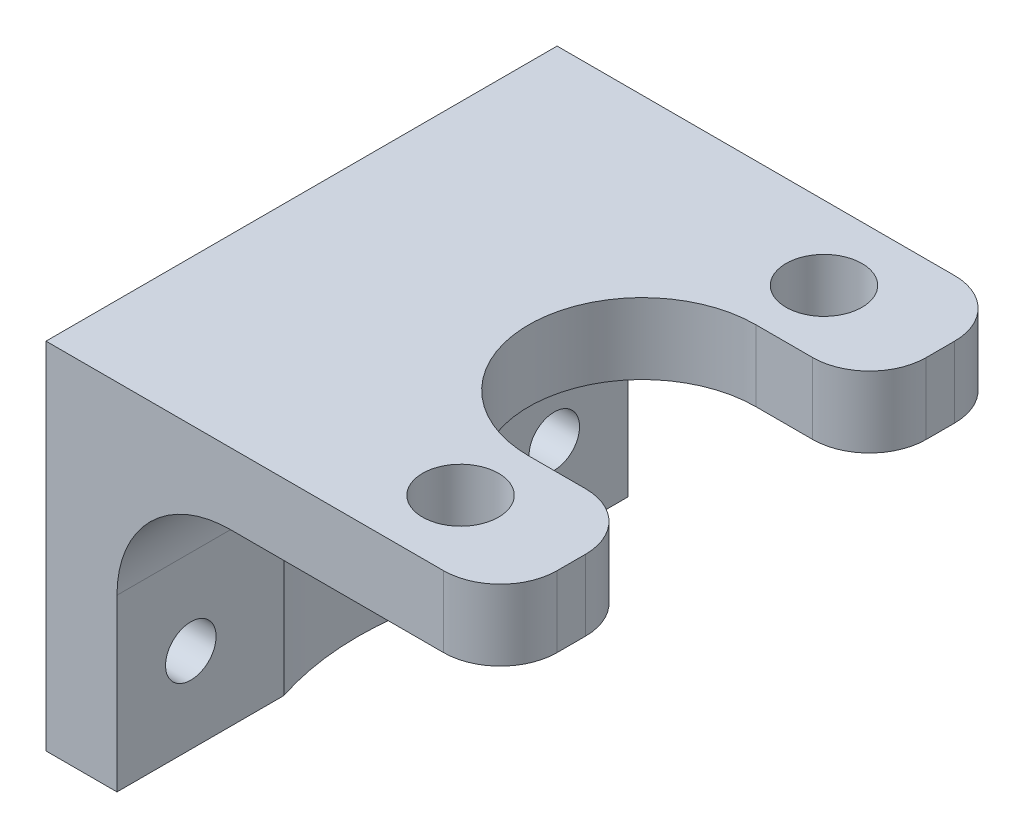
SolidWorks part; units mm, degrees
ref_plane "Front Plane" through (0, 0, 0) normal (0, 0, 1) x (1, 0, 0)
ref_plane "Top Plane" through (0, 0, 0) normal (0, 1, 0) x (1, 0, 0)
ref_plane "Right Plane" through (0, 0, 0) normal (1, 0, 0) x (0, 0, -1)
sketch "Sketch1" plane through (0, 0, 0) normal (0, 1, 0) x (1, 0, 0)
  line L1 (-10.16, -11.43) -> (10.16, -11.43)
  line L2 (-10.16, -11.43) -> (-10.16, 11.43)
  line L3 (-10.16, 11.43) -> (10.16, 11.43)
  line L4 (10.16, -11.43) -> (10.16, 11.43)
  line L5 (-10.16, -11.43) -> (10.16, 11.43) construction
  line L6 (-10.16, 11.43) -> (10.16, -11.43) construction
  point P0 (0, 0)
  dimension "D1" = 20.32
  dimension "D2" = 22.86
extrude "Boss-Extrude1" add sketch "Sketch1" along normal blind 3.175
fillet "Fillet1" radius 2.54 1 edges at (10.16, 1.5875, -11.43) type face fillet first side face at (10.16, 1.5875, 0) second side face at (0, 1.5875, -11.43)
fillet "Fillet2" radius 2.54 1 edges at (10.16, 1.5875, 11.43) type face fillet first side face at (10.16, 1.5875, 1.27) second side face at (0, 1.5875, 11.43)
sketch "Sketch2" plane through (0, 0, 0) normal (0, -1, 0) x (1, 0, 0)
  line L0 (-10.16, -11.43) -> (-10.16, 11.43) construction
  line L1 (7.62, -11.43) -> (-10.16, -11.43) construction
  line L2 (5.08, -5.08) -> (10.16, -5.08)
  line L3 (10.16, 8.89) -> (10.16, -8.89) construction
  line L4 (5.08, 5.08) -> (10.16, 5.08)
  line L5 (10.16, 5.08) -> (10.16, -5.08)
  arc A0 (5.08, 5.08) -> (5.08, -5.08) centre (5.08, 0) ccw
  dimension "D1" = 10.16
  dimension "D2" = 15.24
  dimension "D3" = 11.43
  dimension "D4" = 5.08
extrude "Cut-Extrude2" cut sketch "Sketch2" against normal through all
fillet "Fillet3" radius 2.54 1 edges at (10.16, 1.5875, 5.08) type face fillet first side face at (10.16, 1.5875, 6.985) second side face at (7.62, 1.5875, 5.08)
fillet "Fillet4" radius 2.54 1 edges at (10.16, 1.5875, -5.08) type face fillet first side face at (10.16, 1.5875, -6.985) second side face at (7.62, 1.5875, -5.08)
sketch "Sketch4" plane through (0, 0, 0) normal (0, -1, 0) x (1, 0, 0)
  line L0 (7.62, -11.43) -> (-10.16, -11.43) construction
  line L1 (-10.16, 11.43) -> (-6.985, 11.43)
  line L2 (-10.16, 11.43) -> (-10.16, -11.43)
  line L3 (-10.16, -11.43) -> (-6.985, -11.43)
  line L4 (-6.985, 11.43) -> (-6.985, -11.43)
  dimension "D1" = 3.175
extrude "Boss-Extrude2" add sketch "Sketch4" along normal blind 12.7
fillet "Fillet6" radius 5.08 1 edges type face fillet first side face at (5.3612, 0, -0.9525) second side face at (-6.985, -9.525, -2.8575)
sketch "Sketch3" plane through (0, 0, 0) normal (0, -1, 0) x (1, 0, 0)
  line L0 (7.62, -11.43) -> (-1.905, -11.43) construction
  line L1 (-1.905, 11.43) -> (7.62, 11.43) construction
  line L2 (-10.16, -11.43) -> (-10.16, 11.43) construction
  circle A0 centre (5.08, 8.128) radius 0.9525
  circle A1 centre (5.08, -8.128) radius 0.9525
  dimension "D1" = 16.256
  dimension "D4" = 1.905
  dimension "D5" = 1.905
  dimension "D2" = 3.302
  dimension "D3" = 3.302
  dimension "D6" = 15.24
sketch "Sketch5" plane through (0, 0, 0) normal (0, -1, 0) x (1, 0, 0)
  line L0 (-10.16, 11.43) -> (-10.16, -11.43) construction
  line L1 (7.62, -11.43) -> (-1.905, -11.43) construction
  circle A0 centre (5.08, 0) radius 12.7
  dimension "D1" = 25.4
  dimension "D2" = 15.24
  dimension "D3" = 11.43
extrude "Cut-Extrude4" cut sketch "Sketch5" along normal through all
sketch "Sketch6" plane through (-6.985, 0, 0) normal (1, 0, 0) x (0, 0, -1)
  line L0 (11.43, -12.7) -> (11.43, -5.08) construction
  line L1 (-11.43, -12.7) -> (-11.43, -5.08) construction
  line L2 (11.43, -12.7) -> (3.9656, -12.7) construction
  circle A0 centre (-8.128, -8.89) radius 1.651
  circle A1 centre (8.128, -8.89) radius 1.651
  point P6 (-11.43, -8.89)
  dimension "D1" = 3.302
  dimension "D2" = 3.302
  dimension "D3" = 16.256
  dimension "D4" = 3.302
  dimension "D5" = 3.302
  dimension ".2" = 3.81
hole_wizard "#4-40 Tapped Hole3" positions "Sketch10" profile "Sketch9" tap size "#4-40" standard "ANSI Inch" end condition through all
sketch "Sketch10" plane through (-6.985, 0, 0) normal (1, 0, 0) x (0, 0, -1)
  point P0 (-8.128, -8.89)
  point P3 (8.128, -8.89)
sketch "Sketch9" plane through (-6.985, -8.89, 8.128) normal (0, 1, 0) x (0, 0, -1)
  line L0 (0, 0) -> (0, 3.175)
  line L1 (0, 3.175) -> (1.1303, 3.175)
  line L2 (1.1303, 3.175) -> (1.1303, 0)
  line L5 (1.1303, 0) -> (0, 0)
  line L11 (0, -6.35) -> (0, 107.95) construction
  dimension "Thru Tap Drill Dia." = 2.2606
  dimension "Thru Tap Drill Depth" = 3.175
cosmetic thread "Hole Thread1" parameters "D2"=2.8448
cosmetic thread "Hole Thread2" parameters "D2"=2.8448
hole_wizard "M3 Clearance Hole1" positions "Sketch13" profile "Sketch11" hole size "M3" standard "ANSI Metric" end condition through all
sketch "Sketch13" plane through (0, 0, 0) normal (0, -1, 0) x (-1, 0, 0)
  point P0 (-5.08, -8.128)
  point P3 (-5.08, 8.128)
sketch "Sketch11" plane through (5.08, 0, 8.128) normal (1, 0, 0) x (0, 0, -1)
  line L0 (0, 0) -> (0, 3.175)
  line L1 (0, 3.175) -> (1.7, 3.175)
  line L2 (1.7, 3.175) -> (1.7, 0)
  line L5 (1.7, 0) -> (0, 0)
  line L11 (0, -6.35) -> (0, 107.95) construction
  dimension "Thru Hole Dia." = 3.4
  dimension "Thru Hole Depth" = 3.175
